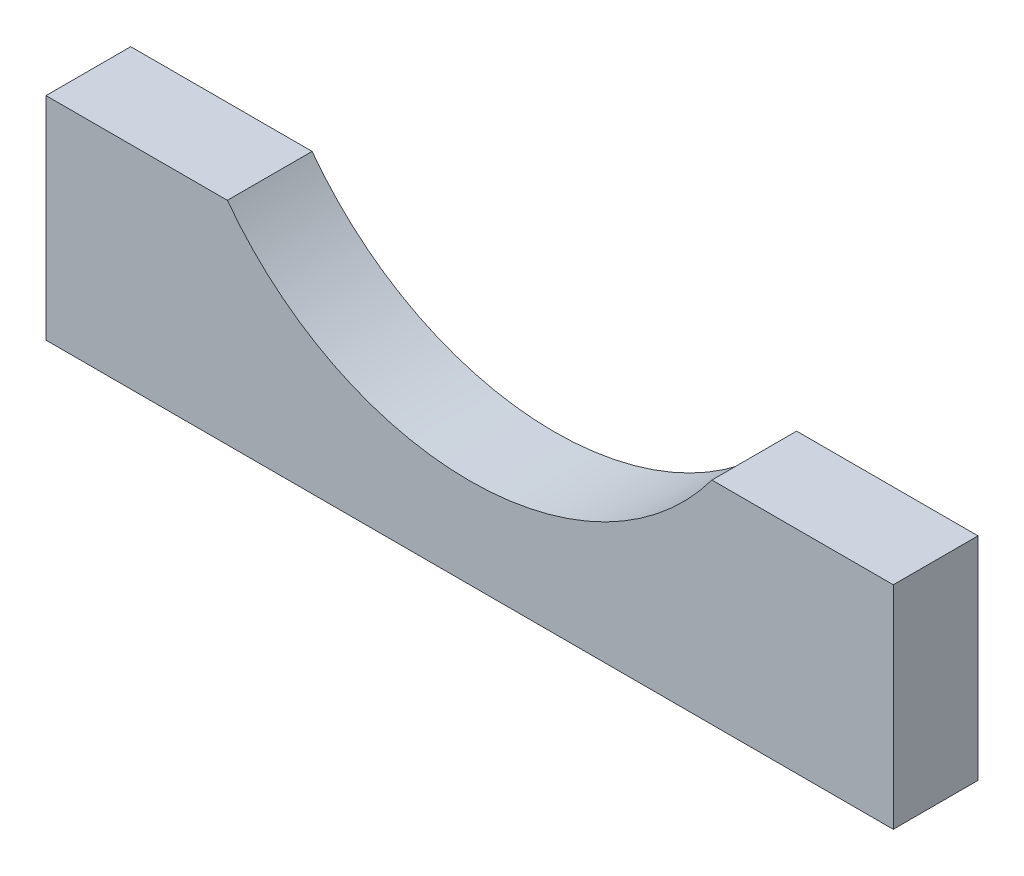
SolidWorks part; units mm, degrees
ref_plane "Front Plane" through (0, 0, 0) normal (0, 0, 1) x (1, 0, 0)
ref_plane "Top Plane" through (0, 0, 0) normal (0, 1, 0) x (1, 0, 0)
ref_plane "Right Plane" through (0, 0, 0) normal (1, 0, 0) x (0, 0, -1)
sketch "Sketch2" plane through (0, 0, 0) normal (0, 0, 1) x (1, 0, 0)
  line L5 (0, 0) -> (40, 0)
  line L6 (40, 0) -> (40, 10)
  line L7 (40, 10) -> (0, 10)
  line L12 (0, 10) -> (0, 0)
  dimension "D1" = 40
  dimension "D2" = 10
extrude "Boss-Extrude2" add sketch "Sketch2" along normal blind 4 contours L12 L5 L6 L7
sketch "Sketch4" plane through (0, 0, 4) normal (0, 0, 1) x (1, 0, 0)
  line L0 (0, 0) -> (40, 0) construction
  line L1 (0, 10) -> (0, 0) construction
  circle A0 centre (20, 18.5) radius 14.25
  dimension "D1" = 18.5
  dimension "D2" = 20
  dimension "D3" = 28.5
extrude "Cut-Extrude1" cut sketch "Sketch4" against normal through all
